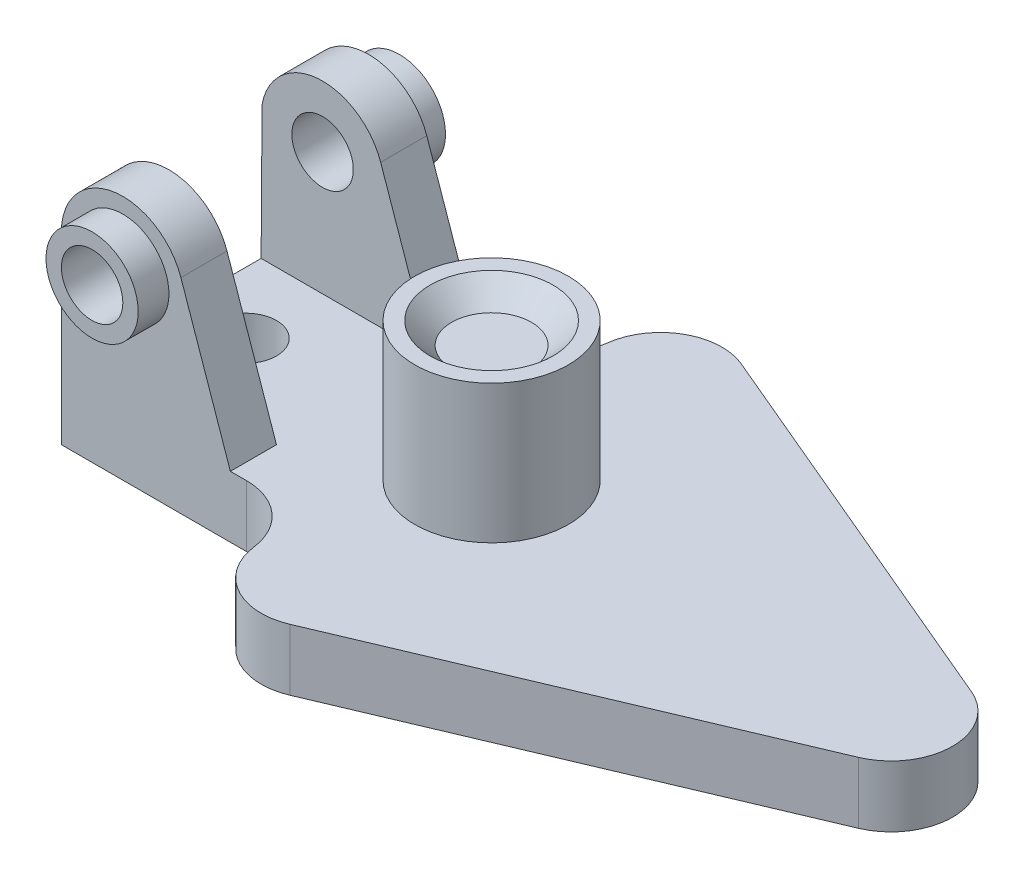
SolidWorks part; units mm, degrees
ref_plane "Front Plane" through (0, 0, 0) normal (0, 0, 1) x (1, 0, 0)
ref_plane "Top Plane" through (0, 0, 0) normal (0, 1, 0) x (1, 0, 0)
ref_plane "Right Plane" through (0, 0, 0) normal (1, 0, 0) x (0, 0, -1)
sketch "Sketch4" plane through (0, 0, 0) normal (0, 1, 0) x (1, 0, 0)
  line L0 (-77.2801, -56.6736) -> (-77.2801, 23.3264)
  line L1 (-77.2801, 23.3264) -> (-16.9664, 23.3264)
  line L2 (30.5127, 56.7457) -> (160.5127, 1.7457)
  line L3 (-77.2801, -16.6736) -> (152.7199, -16.6736) construction
  line L4 (30.5127, -90.0929) -> (160.5127, -35.0929)
  line L5 (-77.2801, -56.6736) -> (-16.9664, -56.6736)
  arc A0 (-16.9664, 23.3264) -> (2.8767, 40.8264) centre (-16.9664, 43.3264) ccw
  arc A1 (2.8767, 40.8264) -> (30.5127, 56.7457) centre (22.7199, 38.3264) cw
  arc A2 (160.5127, -35.0929) -> (160.5127, 1.7457) centre (152.7199, -16.6736) ccw
  circle A3 centre (-57.2801, -16.6736) radius 10
  arc A4 (2.8767, -74.1736) -> (30.5127, -90.0929) centre (22.7199, -71.6736) ccw
  arc A5 (-16.9664, -56.6736) -> (2.8767, -74.1736) centre (-16.9664, -76.6736) cw
  dimension "D2" = 20
  dimension "D5" = 20
  dimension "D6" = 20
  dimension "D7" = 80
  dimension "D8" = 40
  dimension "D1" = 40
  dimension "D3" = 210
  dimension "D4" = 20
  dimension "D9" = 55
extrude "Boss-Extrude1" add sketch "Sketch4" along normal blind 20
sketch "Sketch5" plane through (0, 0, 56.6736) normal (0, 0, 1) x (1, 0, 0)
  line L0 (-77.2801, 20) -> (-77.2801, 60)
  line L1 (-38.3791, 66.5384) -> (-22.2801, 20)
  line L2 (2.8767, 20) -> (-16.9664, 20) construction
  line L3 (-77.2801, 20) -> (-22.2801, 20)
  line L4 (-77.2801, 0) -> (-16.9664, 0) construction
  arc A0 (-77.2801, 60) -> (-38.3791, 66.5384) centre (-57.2801, 60) cw
  circle A1 centre (-57.2801, 60) radius 10
  dimension "D1" = 20
  dimension "D4" = 20
  dimension "D2" = 60
  dimension "D3" = 55
extrude "Boss-Extrude2" add sketch "Sketch5" against normal blind 15
sketch "Sketch6" plane through (0, 0, 56.6736) normal (0, 0, 1) x (1, 0, 0)
  circle A0 centre (-57.2801, 60) radius 15
  circle M8 centre (-57.2801, 60) radius 10
  dimension "D1" = 30
extrude "Boss-Extrude4" add sketch "Sketch6" along normal blind 10 contours M8 | A0 region at (-57.2801, 60, 56.6736)
sketch "Sketch10" plane through (0, 0, -23.3264) normal (0, 0, -1) x (-1, 0, 0)
  line L0 (22.2801, 20) -> (38.3791, 66.5384)
  line L1 (76.969, 63.514) -> (77.2801, 20)
  line L2 (77.2801, 20) -> (22.2801, 20)
  arc A0 (38.3791, 66.5384) -> (76.969, 63.514) centre (57.2801, 60) cw
  arc A1 (77.2801, 60) -> (38.3791, 66.5384) centre (57.2801, 60) ccw construction
  circle A2 centre (57.2801, 60) radius 10
  dimension "D1" = 20
extrude "Boss-Extrude6" add sketch "Sketch10" against normal blind 15
sketch "Sketch11" plane through (0, 0, -23.3264) normal (0, 0, -1) x (-1, 0, 0)
  circle A0 centre (57.2801, 60) radius 15
  circle M8 centre (57.2801, 60) radius 10
  dimension "D1" = 30
extrude "Boss-Extrude7" add sketch "Sketch11" along normal blind 10 contours A0 M8 region at (-42.7044, 60, -23.3264)
sketch "Sketch12" plane through (0, 20, 0) normal (0, 1, 0) x (1, 0, 0)
  line L0 (-77.2801, -16.6736) -> (172.7199, -16.6736) construction
  line L1 (-77.2801, 8.3264) -> (-77.2801, -41.6736) construction
  arc A0 (160.5127, -35.0929) -> (160.5127, 1.7457) centre (152.7199, -16.6736) ccw construction
  circle A1 centre (22.7199, -16.6736) radius 25
  circle A2 centre (-57.2801, -16.6736) radius 10 construction
  dimension "D1" = 80
  dimension "D2" = 50
extrude "Boss-Extrude8" add sketch "Sketch12" along normal blind 45
sketch "Sketch14" plane through (0, 65, 0) normal (0, 1, 0) x (1, 0, 0)
  circle A0 centre (22.7199, -16.6736) radius 20
  dimension "D1" = 40
extrude "Cut-Extrude3" cut sketch "Sketch14" against normal blind 7 draft 45
